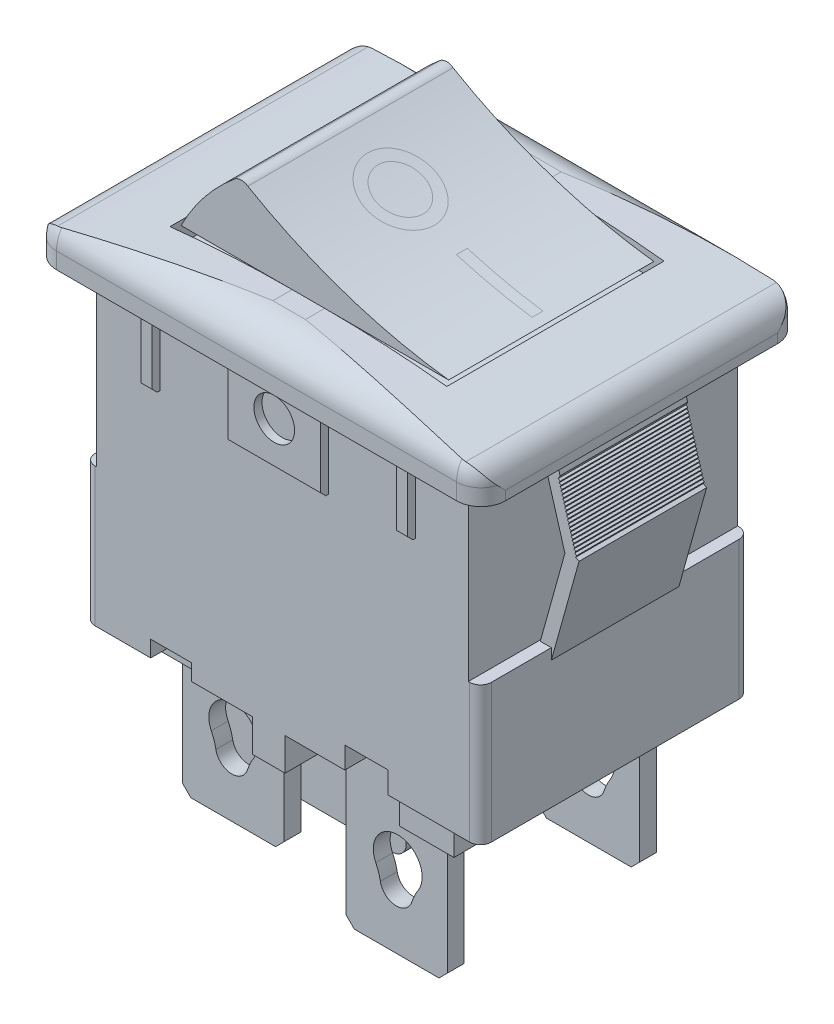
SolidWorks part; units mm, degrees
ref_plane "Front" through (0, 0, 0) normal (0, 0, 1) x (1, 0, 0)
ref_plane "Top" through (0, 0, 0) normal (0, 1, 0) x (1, 0, 0)
ref_plane "Right" through (0, 0, 0) normal (1, 0, 0) x (0, 0, -1)
sketch "Sketch1" plane through (0, 0, 0) normal (0, 0, 1) x (1, 0, 0)
  line L0 (-9.271, -7.366) -> (9.271, -7.366)
  line L1 (-9.271, 7.366) -> (9.271, 7.366)
  line L2 (-9.271, 7.366) -> (-9.271, -7.366)
  line L3 (-9.271, -7.366) -> (9.271, 7.366) construction
  line L4 (9.271, 7.366) -> (9.271, -7.366)
  dimension "D1" = 18.542
  dimension "D3" = 14.732
extrude "Extrude1" add sketch "Sketch1" along normal mid plane 12.5984
sketch "Sketch2" plane through (0, 7.366, 0) normal (0, 1, 0) x (-1, 0, 0)
  line L1 (-10.5029, 7.5057) -> (10.5029, 7.5057)
  line L2 (-10.5029, 7.5057) -> (-10.5029, -7.5057)
  line L3 (-10.5029, -7.5057) -> (10.5029, -7.5057)
  line L4 (10.5029, 7.5057) -> (10.5029, -7.5057)
  point P7 (10.5029, 7.5057)
  point P14 (-10.5029, 7.5057)
  dimension "D1" = 21.0058
  dimension "D2" = 10.5029
  dimension "D3" = 15.0114
  dimension "D4" = 7.5057
extrude "Extrude2" add sketch "Sketch2" along normal blind 2.286
sketch "Sketch16" plane through (0, 0, 0) normal (0, 0, 1) x (1, 0, 0)
  line L0 (0, 0) -> (0, 7.9301) construction
  line L1 (10.5029, 9.652) -> (10.5029, 8.7548)
  line L2 (0.7611, 9.652) -> (10.5029, 9.652)
  line L4 (-10.5029, 7.366) -> (10.5029, 7.366)
  line L5 (10.5029, 7.366) -> (10.5029, 9.652)
  line L6 (10.5029, 9.652) -> (-10.5029, 9.652)
  line L7 (-10.5029, 9.652) -> (-10.5029, 7.366)
  line L10 (-0.7611, 9.652) -> (-10.5029, 9.652)
  line L11 (-10.5029, 9.652) -> (-10.5029, 8.7548)
  arc A0 (-0.7611, 9.652) -> (-10.5029, 8.7548) centre (-0.7611, -43.6823) ccw
  arc A1 (0.7611, 9.652) -> (10.5029, 8.7548) centre (0.7611, -43.6823) cw
  dimension "D1" = 0
extrude "Cut-Extrude5" cut sketch "Sketch16" against normal mid plane 17.78
fillet "Fillet1" radius 1.524 2 edges at (0, 9.652, -7.5057) (0, 9.652, 7.5057) tangent propagation no
fillet "Fillet2" radius 1.143 6 edges at (-10.5029, 7.747, -7.5057) (10.5029, 7.747, -7.5057) (10.5029, 7.747, 7.5057) (-10.5029, 7.747, 7.5057) (-10.5029, 8.7548, 0) (10.5029, 8.7548, 0)
sketch "Sketch19" plane through (0, 0, 0) normal (0, 0, 1) x (1, 0, 0)
  line L0 (-9.271, -7.366) -> (9.271, -7.366) construction
  line L1 (-6.1595, -7.366) -> (-4.2545, -7.366)
  line L2 (-6.1595, -7.366) -> (-6.1595, -6.604)
  line L3 (-6.1595, -6.604) -> (-4.2545, -6.604)
  line L4 (-4.2545, -7.366) -> (-4.2545, -6.604)
  point P6 (-5.207, -7.366)
  dimension "D1" = 1.905
  dimension "D2" = 5.207
  dimension "D3" = 0.762
extrude "Cut-Extrude10" cut sketch "Sketch19" against normal mid plane 15.24
sketch "Sketch20" plane through (0, -7.366, 0) normal (0, -1, 0) x (1, 0, 0)
  line L0 (-6.1595, -6.2992) -> (-6.1595, 6.2992) construction
  line L1 (-6.1595, 4.2672) -> (-8.6995, 4.2672)
  line L2 (-6.1595, 4.2672) -> (-6.1595, 1.7272)
  line L3 (-6.1595, 1.7272) -> (-8.6995, 1.7272)
  line L4 (-8.6995, 4.2672) -> (-8.6995, 1.7272)
  line L5 (-4.2545, 4.2672) -> (-4.2545, 1.7272)
  line L6 (-4.2545, -6.2992) -> (-4.2545, 6.2992) construction
  line L7 (-4.2545, -6.2992) -> (-4.2545, 6.2992) construction
  line L8 (-4.2545, 1.7272) -> (0.127, 1.7272)
  line L9 (0.127, 1.7272) -> (0.127, 6.2992)
  line L10 (0.127, 6.2992) -> (-1.397, 6.2992)
  line L11 (-1.397, 6.2992) -> (-1.397, 4.2672)
  line L12 (-1.397, 4.2672) -> (-4.2545, 4.2672)
  line L14 (4.953, 3.2258) -> (7.493, 3.2258)
  line L15 (4.953, 3.2258) -> (4.953, 5.7658)
  line L16 (4.953, 5.7658) -> (7.493, 5.7658)
  line L17 (7.493, 3.2258) -> (7.493, 5.7658)
  line L18 (-4.2545, 6.2992) -> (9.271, 6.2992) construction
  line L19 (-9.271, 6.2992) -> (-9.271, -6.2992) construction
  line L20 (9.271, 6.2992) -> (9.271, -6.2992) construction
  point P20 (7.493, 4.4958)
  point P21 (-8.6995, 2.9972)
  dimension "D1" = 2.54
  dimension "D2" = 2.54
  dimension "D3" = 4.4958
  dimension "D4" = 2.54
  dimension "D5" = 2.54
  dimension "D6" = 2.9972
  dimension "D7" = 1.524
  dimension "D8" = 9.398
  dimension "D9" = 1.778
  dimension "D10" = 2.54
extrude "Boss-Extrude1" add sketch "Sketch20" along normal blind 1.524
sketch "Sketch21" plane through (0, 0, 6.2992) normal (0, 0, 1) x (1, 0, 0)
  line L0 (0.127, -7.366) -> (9.271, -7.366) construction
  line L1 (2.921, -7.366) -> (4.953, -7.366)
  line L2 (2.921, -7.366) -> (2.921, -6.35)
  line L3 (2.921, -6.35) -> (4.953, -6.35)
  line L4 (4.953, -7.366) -> (4.953, -6.35)
  point P6 (3.937, -7.366)
  dimension "D1" = 2.032
  dimension "D2" = 3.937
extrude "Cut-Extrude11" cut sketch "Sketch21" against normal blind 1.905
sketch "Sketch22" plane through (0, -6.604, 0) normal (0, -1, 0) x (1, 0, 0)
  line L1 (-9.271, 6.2992) -> (-9.271, -6.2992) construction
  line L2 (-9.271, 0.508) -> (0, 0.508)
  line L3 (-9.271, 0.508) -> (-9.271, -0.508)
  line L4 (-9.271, -0.508) -> (0, -0.508)
  line L5 (0, 0.508) -> (0, -0.508)
  dimension "D1" = 1.016
  dimension "D2" = 0.508
extrude "Boss-Extrude2" add sketch "Sketch22" along normal blind 8.763
fillet "Fillet3" radius 0.635 2 edges at (0, -15.367, 0) (-9.271, -15.367, 0)
mirror "Mirror3" about plane through (0, 0, 0) normal (0, 0, 1) of "Cut-Extrude11", "Boss-Extrude1"
sketch "Sketch3" plane through (0, -6.604, 0) normal (0, -1, 0) x (1, 0, 0)
  line L0 (-8.6995, 2.9972) -> (-6.1595, 2.9972) construction
  line L1 (-8.6995, 4.2672) -> (-8.6995, 1.7272) construction
  line L2 (-7.5819, 2.9972) -> (-2.8321, 2.9972) construction
  line L3 (-7.5819, 3.3909) -> (-7.5819, 2.6035)
  line L4 (-7.5819, 3.3909) -> (-2.8321, 3.3909)
  line L5 (-2.8321, 3.3909) -> (-2.8321, 2.6035)
  line L6 (-7.5819, 2.6035) -> (-2.8321, 2.6035)
  line L7 (-6.1595, 1.7272) -> (-6.1595, 4.2672) construction
  line L8 (7.493, 4.4958) -> (2.6964, 4.4958) construction
  line L9 (7.493, 3.2258) -> (7.493, 5.7658) construction
  line L10 (3.937, 6.2992) -> (3.937, 1.5161) construction
  line L11 (4.953, 6.2992) -> (2.921, 6.2992) construction
  line L12 (-5.207, 3.3909) -> (-5.207, 2.6035) construction
  line L13 (1.5621, 4.8895) -> (1.5621, 4.1021)
  line L14 (1.5621, 4.1021) -> (6.3119, 4.1021)
  line L15 (3.937, 4.8895) -> (3.937, 4.1021) construction
  line L16 (6.3119, 4.8895) -> (6.3119, 4.1021)
  line L17 (1.5621, 4.8895) -> (6.3119, 4.8895)
  line L18 (1.5621, 4.4958) -> (6.3119, 4.4958) construction
  point P1 (-5.207, 3.3909)
  dimension "D1" = 4.7498
  dimension "D3" = 0.7874
  dimension "D4" = 5.207
extrude "Extrude3" add sketch "Sketch3" along normal blind 8.763
chamfer "Chamfer1" distance 0.762 angle 45 4 edges at (-7.5819, -15.367, 2.9972) (-2.8321, -15.367, 2.9972) (1.5621, -15.367, 4.4958) (6.3119, -15.367, 4.4958)
chamfer "Chamfer2" distance 0.3683 angle 45 4 edges at (-5.207, -15.367, 2.6035) (-5.207, -15.367, 3.3909) (3.937, -15.367, 4.8895) (3.937, -15.367, 4.1021)
sketch "Sketch23" plane through (0, 0, 2.6035) normal (0, 0, 1) x (1, 0, 0)
  line L0 (-0.635, -15.367) -> (-8.636, -15.367) construction
  arc A0 (-4.2498, -11.9276) -> (-6.2341, -11.8044) centre (-5.207, -11.303) ccw
  arc A1 (-6.0192, -12.4559) -> (-4.5437, -12.5475) centre (-5.27, -12.317) ccw
  arc A2 (-6.0192, -12.4559) -> (-6.2341, -11.8044) centre (-8.5167, -12.9187) ccw
  arc A3 (-4.5437, -12.5475) -> (-4.2498, -11.9276) centre (-2.1226, -13.3157) cw
  arc A4 (4.945, -11.9276) -> (2.9607, -11.8044) centre (3.9878, -11.303) ccw
  arc A5 (3.1756, -12.4559) -> (4.6511, -12.5475) centre (3.9248, -12.317) ccw
  arc A6 (3.1756, -12.4559) -> (2.9607, -11.8044) centre (0.6781, -12.9187) ccw
  arc A7 (4.6511, -12.5475) -> (4.945, -11.9276) centre (7.0722, -13.3157) cw
  dimension "D1" = 2.286
  dimension "D2" = 1.524
  dimension "D5" = 2.54
  dimension "D3" = 1.016
  dimension "D4" = 4.064
  dimension "D6" = 2
extrude "Cut-Extrude12" cut sketch "Sketch23" along normal through all
mirror "Mirror4" about plane through (0, 0, 0) normal (0, 0, 1) of "Cut-Extrude12", "Chamfer2", "Chamfer1", "Extrude3"
sketch "Sketch18" plane through (0, 9.652, 0) normal (0, 1, 0) x (1, 0, 0)
  line L1 (-6.477, 5.08) -> (6.477, 5.08)
  line L2 (-6.477, 5.08) -> (-6.477, -5.08)
  line L3 (-6.477, -5.08) -> (6.477, -5.08)
  line L4 (6.477, 5.08) -> (6.477, -5.08)
  line L5 (-6.477, 5.08) -> (6.477, -5.08) construction
  line L6 (-6.477, -5.08) -> (6.477, 5.08) construction
  point P0 (0, 0)
  dimension "D1" = 12.954
  dimension "D2" = 10.16
extrude "Cut-Extrude9" cut sketch "Sketch18" against normal blind 1.27
sketch "Sketch6" plane through (0, 0, 0) normal (0, 0, 1) x (1, 0, 0)
  line L1 (-6.2422, 9.3696) -> (6.2791, 9.3696)
  arc A0 (-3.1134, 12.5233) -> (6.2791, 9.3696) centre (9.24, 33.7511) ccw
  arc A2 (-3.738, 12.5029) -> (-6.2422, 9.3696) centre (2.6878, 4.8) ccw
  arc A3 (-3.1134, 12.5233) -> (-3.738, 12.5029) centre (-3.4126, 12.1128) ccw
  arc A4 (-0.7611, 9.652) -> (-9.3599, 8.9543) centre (-0.7611, -43.6823) ccw construction
  point P10 (-3.7306, 10.9605)
  dimension "D1" = 0.508
  dimension "D2" = 3.2512
extrude "Extrude4" add sketch "Sketch6" along normal mid plane 9.6012
sketch "Sketch10" plane through (0, 0, 6.2992) normal (0, 0, 1) x (1, 0, 0)
  line L0 (9.271, 7.366) -> (-9.271, 7.366) construction
  line L1 (6.2357, 7.366) -> (5.7277, 7.366)
  line L2 (6.2357, 7.366) -> (6.2357, 3.683)
  line L3 (6.2357, 3.683) -> (5.7277, 3.683)
  line L4 (5.7277, 7.366) -> (5.7277, 3.683)
  line L5 (-9.3599, 7.366) -> (9.3599, 7.366) construction
  line L6 (-6.2357, 7.366) -> (-5.7277, 7.366)
  line L7 (-6.2357, 7.366) -> (-6.2357, 3.683)
  line L8 (-6.2357, 3.683) -> (-5.7277, 3.683)
  line L9 (-5.7277, 7.366) -> (-5.7277, 3.683)
  line L10 (-6.2357, -5.1308) -> (-6.2357, 11.8605) construction
  line L11 (6.2357, -5.1308) -> (6.2357, 12.4797) construction
  line L12 (9.271, 7.366) -> (-9.271, 7.366) construction
  line L13 (2.159, 3.429) -> (-2.159, 3.429)
  line L14 (2.159, 3.429) -> (2.159, 7.366)
  line L15 (2.159, 7.366) -> (-2.159, 7.366)
  line L16 (-2.159, 3.429) -> (-2.159, 7.366)
  line L17 (0, 7.366) -> (0, 3.429) construction
  circle A0 centre (0, 5.5946) radius 0.9525
  dimension "D5" = 1.905
  dimension "D1" = 0.508
  dimension "D2" = 0.508
  dimension "D3" = 3.683
  dimension "D4" = 4.318
extrude "Extrude7" add sketch "Sketch10" along normal blind 0.381
chamfer "Chamfer4" distance 0.254 angle 45 3 edges at (0, 3.429, 6.6802) (5.9817, 3.683, 6.6802) (-5.9817, 3.683, 6.6802)
mirror "Mirror1" about plane through (0, 0, 0) normal (0, 0, 1) of "Chamfer4", "Extrude7"
sketch "Sketch17" plane through (0, 0, 0) normal (0, 0, 1) x (1, 0, 0)
  line L1 (-9.271, 7.366) -> (-8.6995, 7.366)
  line L2 (-9.271, 7.366) -> (-9.271, -0.889)
  line L3 (-9.271, -0.889) -> (-8.6995, -0.889)
  line L4 (-8.6995, 7.366) -> (-8.6995, -0.889)
  line L5 (9.271, 7.366) -> (8.6995, 7.366)
  line L6 (9.271, 7.366) -> (9.271, -0.889)
  line L7 (9.271, -0.889) -> (8.6995, -0.889)
  line L8 (8.6995, 7.366) -> (8.6995, -0.889)
  dimension "D1" = 17.399
extrude "Cut-Extrude6" cut sketch "Sketch17" against normal mid plane 15.24
sketch "Sketch12" plane through (0, 0, 0) normal (0, 0, 1) x (1, 0, 0)
  line L0 (9.271, -7.366) -> (9.271, -0.889) construction
  line L2 (8.6592, -1.2268) -> (9.9053, 3.2518)
  line L3 (9.9053, 3.2518) -> (8.6981, 7.366)
  line L4 (9.9053, 3.2518) -> (8.7506, 7.1872) construction
  line L5 (9.271, -1.397) -> (10.5657, 3.2565)
  line L6 (10.5657, 3.2565) -> (9.3599, 7.366)
  line L7 (-9.3599, 7.366) -> (9.3599, 7.366) construction
  line L8 (8.6981, 7.366) -> (9.3599, 7.366)
  line L9 (0, 0) -> (0, 11.7131) construction
  line L10 (9.271, -1.397) -> (8.6592, -1.2268)
  line L13 (-9.271, -1.397) -> (-8.6592, -1.2268)
  line L14 (-8.6981, 7.366) -> (-9.3599, 7.366)
  line L15 (-10.5657, 3.2565) -> (-9.3599, 7.366)
  line L16 (-9.271, -1.397) -> (-10.5657, 3.2565)
  line L17 (-9.9053, 3.2518) -> (-8.6981, 7.366)
  line L18 (-8.6592, -1.2268) -> (-9.9053, 3.2518)
  dimension "D2" = 0.635
extrude "Extrude9" add sketch "Sketch12" along normal mid plane 5.969
sketch "Sketch13" plane through (0, 0, 2.9845) normal (0, 0, 1) x (1, 0, 0)
  line L0 (10.5657, 3.2565) -> (9.3599, 7.366) construction
  line L1 (10.5657, 3.2565) -> (10.4942, 3.5002)
  line L2 (10.5657, 3.2565) -> (10.4081, 3.3426)
  line L3 (10.4081, 3.3426) -> (10.4942, 3.5002)
  dimension "D1" = 90
  dimension "D2" = 0.127
  dimension "D3" = 45
  dimension "D4" = 0.254
extrude "Cut-Extrude3" cut sketch "Sketch13" against normal through all
pattern_linear "LPattern4" count 20 spacing 0.1524 along (-0.2815, 0.9595, 0) of "Cut-Extrude3"
mirror "Mirror2" about plane through (0, 0, 0) normal (1, 0, 0) of "LPattern4", "Cut-Extrude3"
fillet "Fillet4" radius 0.508 4 edges at (9.271, -4.1275, 6.2992) (-9.271, -4.1275, 6.2992) (-9.271, -4.1275, -6.2992) (9.271, -4.1275, -6.2992)
ref_plane "Plane1" through (8.9344, 8.9345, 0) normal (-0.7071, -0.7071, 0) x (-0.7071, 0.7071, 0)
sketch "Sketch24" plane through (8.9344, 8.9345, 0) normal (-0.7071, -0.7071, 0) x (-0.7071, 0.7071, 0)
  line L0 (1.4331, -0.127) -> (9.4269, -0.127) construction
  line L1 (2.5994, 0.127) -> (5.6474, 0.127)
  line L2 (2.5994, 0.127) -> (2.5994, -0.381)
  line L3 (2.5994, -0.381) -> (5.6474, -0.381)
  line L4 (5.6474, 0.127) -> (5.6474, -0.381)
  line L5 (2.5994, 0.127) -> (5.6474, -0.381) construction
  line L6 (2.5994, -0.381) -> (5.6474, 0.127) construction
  circle A0 centre (8.4414, -0.127) radius 1.5875
  circle A1 centre (8.4414, -0.127) radius 1.0795
  point P3 (4.1234, -0.127)
  dimension "D1" = 3.048
  dimension "D3" = 3.175
  dimension "D4" = 2.159
  dimension "D2" = 0.508
  dimension "D5" = 4.318
split line "Split Line1"
